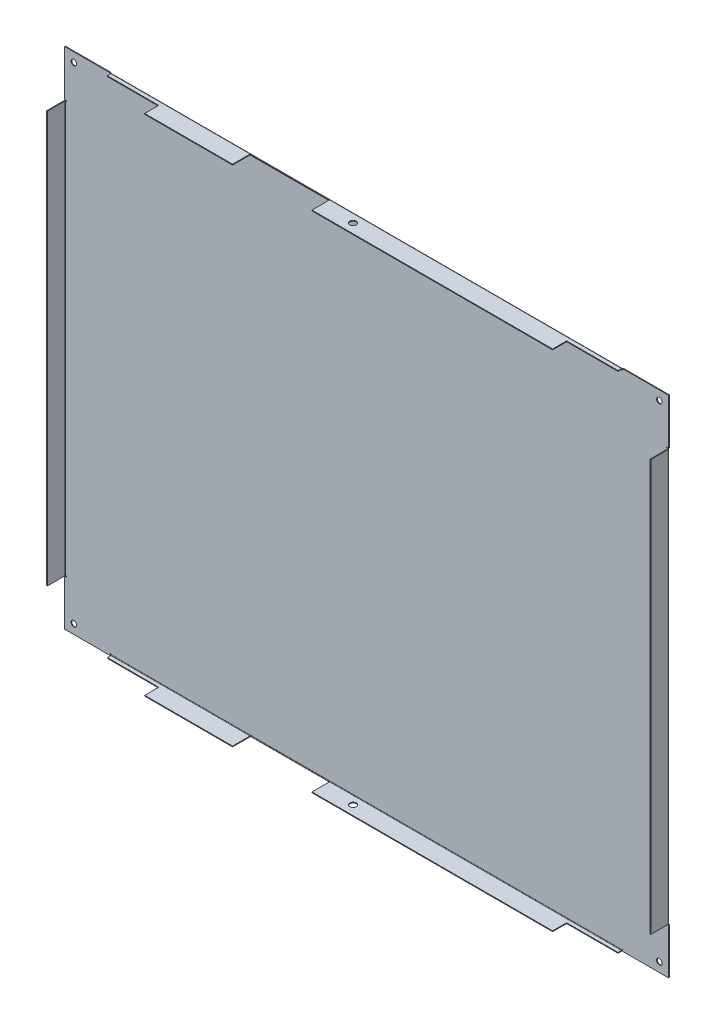
SolidWorks part; units mm, degrees
note: The reader was unsure of these and kept them because the rebuilt part matched: flange length of "边线-法兰1", "边线-法兰2", "边线-法兰3", "边线-法兰4".
ref_plane "前视基准面" through (0, 0, 0) normal (0, 0, 1) x (1, 0, 0)
ref_plane "上视基准面" through (0, 0, 0) normal (0, 1, 0) x (1, 0, 0)
ref_plane "右视基准面" through (0, 0, 0) normal (1, 0, 0) x (0, 0, -1)
sketch "草图1" plane through (0, 0, 0) normal (0, 0, 1) x (1, 0, 0)
  line L1 (-323.25, 270) -> (323.25, 270)
  line L2 (-323.25, 270) -> (-323.25, -270)
  line L3 (-323.25, -270) -> (323.25, -270)
  line L4 (323.25, 270) -> (323.25, -270)
  line L5 (-323.25, 270) -> (323.25, -270) construction
  line L6 (-323.25, -270) -> (323.25, 270) construction
  circle A0 centre (313.25, 260) radius 3
  circle A1 centre (-313.25, 260) radius 3
  circle A2 centre (-313.25, -260) radius 3
  circle A3 centre (313.25, -260) radius 3
  point P0 (0, 0)
  dimension "D11" = 6
  dimension "D1" = 646.5
  dimension "D2" = 540
  dimension "D3" = 10
  dimension "D4" = 10
  dimension "D5" = 10
  dimension "D6" = 10
  dimension "D7" = 10
  dimension "D8" = 10
  dimension "D9" = 10
  dimension "D10" = 10
base flange "基体-法兰1" sketch "草图1" thickness 0.8 reverse thickness direction no parameters "D1"=0.5
edge flange "边线-法兰1" sketch "草图8" flange angle 90 flange length 20 flange position material inside bend radius 0.5 thickness 0.8 parameters "D6"=10
sketch "草图8" plane through (323.25, 0, 0) normal (1, 0, 0) x (0, 1, 0)
  line L2 (-220, 0) -> (-220, 19.2)
  line L3 (-220, 19.2) -> (220, 19.2)
  line L4 (220, 19.2) -> (220, 0)
  line L5 (-270, 0) -> (270, 0) construction
  line L6 (-220, 0) -> (220, 0)
  line L7 (270, -0.8) -> (270, 0) construction
  line L8 (-270, -0.8) -> (-270, 0) construction
  dimension "D1" = 50
  dimension "D2" = 50
bend "边线折弯1" bend radius 0.5 bend angle 90 parameters "D5"=1
edge flange "边线-法兰2" sketch "草图11" flange angle 90 flange length 20 flange position material inside bend radius 0.5 thickness 0.8 parameters "D6"=10
sketch "草图11" plane through (-323.25, 0, 0) normal (-1, 0, 0) x (0, -1, 0)
  line L0 (-270, 0) -> (270, 0) construction
  line L1 (-220, 0) -> (220, 0)
  line L2 (-220, 0) -> (-220, 19.2)
  line L3 (-220, 19.2) -> (220, 19.2)
  line L4 (220, 19.2) -> (220, 0)
  line L5 (270, -0.8) -> (270, 0) construction
  line L6 (-270, -0.8) -> (-270, 0) construction
  line L7 (-270, -0.8) -> (270, -0.8) construction
  dimension "D1" = 50
  dimension "D2" = 50
  dimension "D3" = 20
bend "边线折弯2" bend radius 0.5 bend angle 90 parameters "D5"=2
edge flange "边线-法兰3" sketch "草图14" flange angle 90 flange length 20 flange position material inside bend radius 0.5 thickness 0.8 parameters "D6"=10
sketch "草图14" plane through (0, -270, 0) normal (0, -1, 0) x (1, 0, 0)
  line L2 (-273.25, 0) -> (-273.25, 4.2)
  line L3 (-218.25, 19.2) -> (218.25, 19.2)
  line L4 (273.25, 4.2) -> (273.25, 0)
  line L5 (-323.25, 0) -> (323.25, 0) construction
  line L6 (-273.25, 0) -> (273.25, 0)
  line L7 (323.25, -0.8) -> (323.25, 0) construction
  line L8 (-323.25, -0.8) -> (-323.25, 0) construction
  line L9 (218.25, 19.2) -> (218.25, 4.2)
  line L10 (218.25, 4.2) -> (273.25, 4.2)
  line L12 (-273.25, 4.2) -> (-218.25, 4.2)
  line L13 (-323.25, -0.8) -> (323.25, -0.8) construction
  line L15 (-218.25, 4.2) -> (-218.25, 19.2)
  dimension "D1" = 55
  dimension "D2" = 5
  dimension "D3" = 50
  dimension "D4" = 55
  dimension "D5" = 5
  dimension "D6" = 50
  dimension "D7" = 20
bend "边线折弯3" bend radius 0.5 bend angle 90 parameters "D5"=3
edge flange "边线-法兰4" sketch "草图17" flange angle 90 flange length 20 flange position material inside bend radius 0.5 thickness 0.8 parameters "D6"=10
sketch "草图17" plane through (0, 270, 0) normal (0, 1, 0) x (-1, 0, 0)
  line L2 (-273.25, 0) -> (-273.25, 4.2)
  line L3 (-218.25, 19.2) -> (218.25, 19.2)
  line L4 (273.25, 4.2) -> (273.25, 0)
  line L5 (-323.25, 0) -> (323.25, 0) construction
  line L6 (-273.25, 0) -> (273.25, 0)
  line L7 (-323.25, -0.8) -> (323.25, -0.8) construction
  line L8 (323.25, -0.8) -> (323.25, 0) construction
  line L9 (-323.25, -0.8) -> (-323.25, 0) construction
  line L10 (273.25, 4.2) -> (218.25, 4.2)
  line L11 (218.25, 19.2) -> (218.25, 4.2)
  line L14 (-273.25, 4.2) -> (-218.25, 4.2)
  line L15 (-218.25, 19.2) -> (-218.25, 4.2)
  dimension "D1" = 55
  dimension "D2" = 5
  dimension "D3" = 50
  dimension "D4" = 5
  dimension "D5" = 55
  dimension "D6" = 50
  dimension "D7" = 20
bend "边线折弯4" bend radius 0.5 bend angle 90 parameters "D5"=4
sketch "草图18" plane through (0, -269.2, 0) normal (0, 1, 0) x (1, 0, 0)
  line L0 (-119.2127, -3.0736) -> (-119.2127, -28.5736) construction
  line L1 (-124.2127, -42.3234) -> (-39.2127, -42.3234)
  line L2 (-124.2127, -42.3234) -> (-124.2127, 0)
  line L3 (-124.2127, 0) -> (-39.2127, 0)
  line L4 (-39.2127, -42.3234) -> (-39.2127, 0)
  line L5 (-44.2127, -3.0736) -> (-44.2127, -28.5736) construction
  line L6 (273.25, 0) -> (-273.25, 0) construction
  dimension "D1" = 5
  dimension "D2" = 5
extrude "切除-拉伸1" cut sketch "草图18" against normal through all
sketch "草图19" plane through (0, 269.2, 0) normal (0, -1, 0) x (1, 0, 0)
  line L0 (-44.2127, 2.9264) -> (-44.2127, 28.4264) construction
  line L1 (-124.2127, 0) -> (-39.2127, 0)
  line L2 (-124.2127, 0) -> (-124.2127, 50.9464)
  line L3 (-124.2127, 50.9464) -> (-39.2127, 50.9464)
  line L4 (-39.2127, 0) -> (-39.2127, 50.9464)
  line L5 (-119.2127, 2.9264) -> (-119.2127, 28.4264) construction
  line L6 (-273.25, 0) -> (273.25, 0) construction
  dimension "D1" = 5
  dimension "D2" = 5
extrude "切除-拉伸2" cut sketch "草图19" against normal through all
sketch "草图20" plane through (0, -270, 0) normal (0, -1, 0) x (-1, 0, 0)
  line L0 (-273.25, 0.8) -> (273.25, 0.8) construction
  line L1 (-323.25, -19.2) -> (-323.25, -0.5) construction
  circle A0 centre (5.25, -9.2) radius 3.5
  dimension "D3" = 7
  dimension "D1" = 10
  dimension "D2" = 328.5
extrude "切除-拉伸3" cut sketch "草图20" against normal through all
sketch "折弯-线1" plane through (0, 0, 0) normal (0, 1, 0) x (1, 0, 0)
sketch "边界框1" plane through (0, 0, 0) normal (0, 1, 0) x (1, 0, 0)
sheet metal parameters "钣金1" thickness 0.8 parameters "D1"=0.5
flat pattern "平板型式1" [suppressed]
sketch "折弯-线2" plane through (0, 0, 0) normal (0, 1, 0) x (1, 0, 0)
sketch "边界框2" [suppressed] plane through (0, 0, 0) normal (0, 1, 0) x (1, 0, 0)
sheet metal parameters "钣金2" thickness 0.8 parameters "D1"=0.5
flat pattern "平板型式1" [suppressed]
sketch "折弯-线2" plane through (0, 0, 0) normal (0, 1, 0) x (1, 0, 0)
sketch "边界框2" [suppressed] plane through (0, 0, 0) normal (0, 1, 0) x (1, 0, 0)
bend of the flat pattern "展开-<边线折弯1>1"
sheet metal parameters "钣金3" thickness 0.8 parameters "D1"=0.5
flat pattern "平板型式1" [suppressed]
sketch "折弯-线2" plane through (0, 0, 0) normal (0, 1, 0) x (1, 0, 0)
sketch "边界框2" [suppressed] plane through (0, 0, 0) normal (0, 1, 0) x (1, 0, 0)
bend of the flat pattern "展开-<边线折弯1>1"
bend of the flat pattern "展开-<边线折弯2>1"
sheet metal parameters "钣金4" thickness 0.8 parameters "D1"=0.5
flat pattern "平板型式1" [suppressed]
sketch "折弯-线2" plane through (0, 0, 0) normal (0, 1, 0) x (1, 0, 0)
sketch "边界框2" [suppressed] plane through (0, 0, 0) normal (0, 1, 0) x (1, 0, 0)
bend of the flat pattern "展开-<边线折弯1>1"
bend of the flat pattern "展开-<边线折弯2>1"
bend of the flat pattern "展开-<边线折弯3>1"
sheet metal parameters "钣金5" thickness 0.8 parameters "D1"=0.5
flat pattern "平板型式1" [suppressed]
sketch "折弯-线2" plane through (0, 0, 0) normal (0, 1, 0) x (1, 0, 0)
sketch "边界框2" [suppressed] plane through (0, 0, 0) normal (0, 1, 0) x (1, 0, 0)
bend of the flat pattern "展开-<边线折弯1>1"
bend of the flat pattern "展开-<边线折弯2>1"
bend of the flat pattern "展开-<边线折弯3>1"
bend of the flat pattern "展开-<边线折弯4>1"
sheet metal parameters "钣金6" thickness 0.8 parameters "D1"=0.5
flat pattern "平板型式1" [suppressed]
sketch "折弯-线2" plane through (0, 0, 0) normal (0, 1, 0) x (1, 0, 0)
sketch "边界框2" [suppressed] plane through (0, 0, 0) normal (0, 1, 0) x (1, 0, 0)
bend of the flat pattern "展开-<边线折弯1>1"
bend of the flat pattern "展开-<边线折弯2>1"
bend of the flat pattern "展开-<边线折弯3>1"
bend of the flat pattern "展开-<边线折弯4>1"
sheet metal parameters "钣金7" thickness 0.8 parameters "D1"=0.5
flat pattern "平板型式1" [suppressed]
sketch "折弯-线2" plane through (0, 0, 0) normal (0, 1, 0) x (1, 0, 0)
sketch "边界框2" [suppressed] plane through (0, 0, 0) normal (0, 1, 0) x (1, 0, 0)
bend of the flat pattern "展开-<边线折弯1>1"
bend of the flat pattern "展开-<边线折弯2>1"
bend of the flat pattern "展开-<边线折弯3>1"
bend of the flat pattern "展开-<边线折弯4>1"
sheet metal parameters "钣金8" thickness 0.8 parameters "D1"=0.5
flat pattern "平板型式1" [suppressed]
sketch "折弯-线2" plane through (0, 0, 0) normal (0, 1, 0) x (1, 0, 0)
sketch "边界框2" [suppressed] plane through (0, 0, 0) normal (0, 1, 0) x (1, 0, 0)
bend of the flat pattern "展开-<边线折弯1>1"
bend of the flat pattern "展开-<边线折弯2>1"
bend of the flat pattern "展开-<边线折弯3>1"
bend of the flat pattern "展开-<边线折弯4>1"
